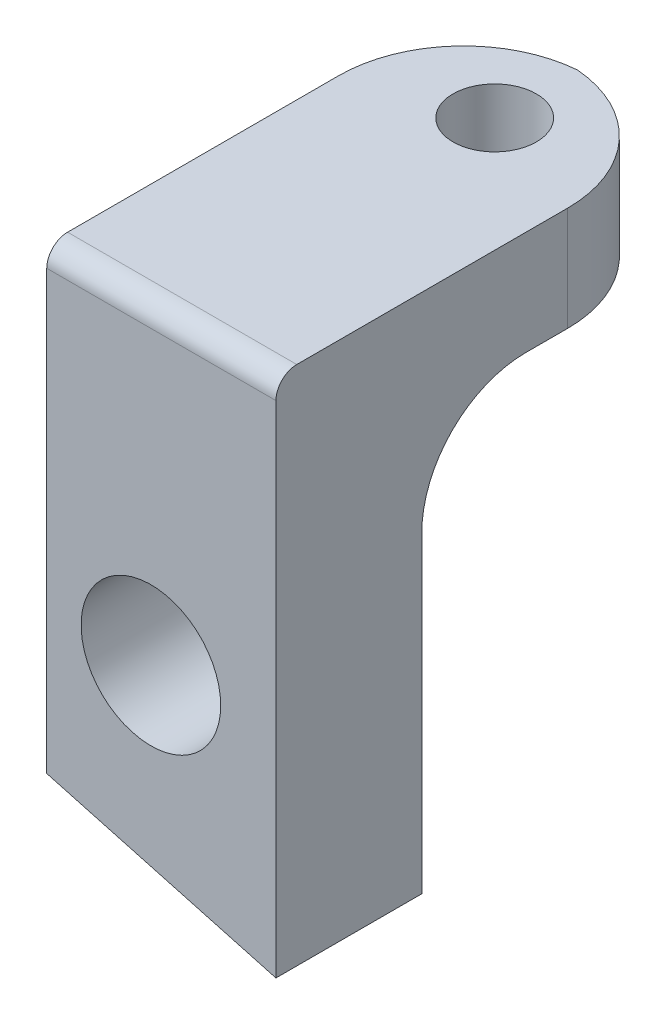
SolidWorks part; units mm, degrees
ref_plane "Спереди" through (0, 0, 0) normal (0, 0, 1) x (1, 0, 0)
ref_plane "Сверху" through (0, 0, 0) normal (0, 1, 0) x (1, 0, 0)
ref_plane "Справа" through (0, 0, 0) normal (1, 0, 0) x (0, 0, -1)
sketch "Эскиз1" plane through (0, 0, 0) normal (0, 0, 1) x (1, 0, 0)
  line L1 (-5, 10) -> (6, 10)
  line L2 (-5, 10) -> (-5, -7)
  line L3 (-5, -7) -> (6, -10)
  line L4 (6, 10) -> (6, -10)
  circle A0 centre (0, 0) radius 3.35
  dimension "D1" = 6.7
  dimension "D2" = 11
  dimension "D3" = 6
  dimension "D4" = 10
  dimension "D5" = 3
  dimension "D6" = 20
extrude "Бобышка-Вытянуть1" add sketch "Эскиз1" along normal blind 7
sketch "Эскиз2" plane through (0, 10, 0) normal (0, 1, 0) x (1, 0, 0)
  line L1 (-5, -7) -> (6, -7)
  line L2 (-5, -7) -> (-5, 13)
  line L3 (-5, 13) -> (6, 13)
  line L4 (6, -7) -> (6, 13)
  dimension "D1" = 11
  dimension "D2" = 20
extrude "Бобышка-Вытянуть2" add sketch "Эскиз2" along normal blind 5
fillet "Скругление1" radius 5 1 edges at (0.5, 10, 0)
fillet "Скругление2" radius 1 1 edges at (3.35, 0, 0)
fillet "Скругление4" radius 1 1 edges at (0.5, 15, 7)
sketch "Эскиз3" plane through (0, 10, 0) normal (0, -1, 0) x (1, 0, 0)
  line L0 (0.5, -13) -> (0.5, -5) construction
  line L7 (6, -13) -> (-5, -13) construction
  line L8 (6, -5) -> (-5, -5) construction
  circle A0 centre (0.5, -9) radius 2
  dimension "D1" = 4
fillet "Скругление11" radius 6 2 edges at (6, 12.5, -13) (-5, 12.5, -13)
extrude "Вырез-Вытянуть2" cut sketch "Эскиз3" against normal blind 10
